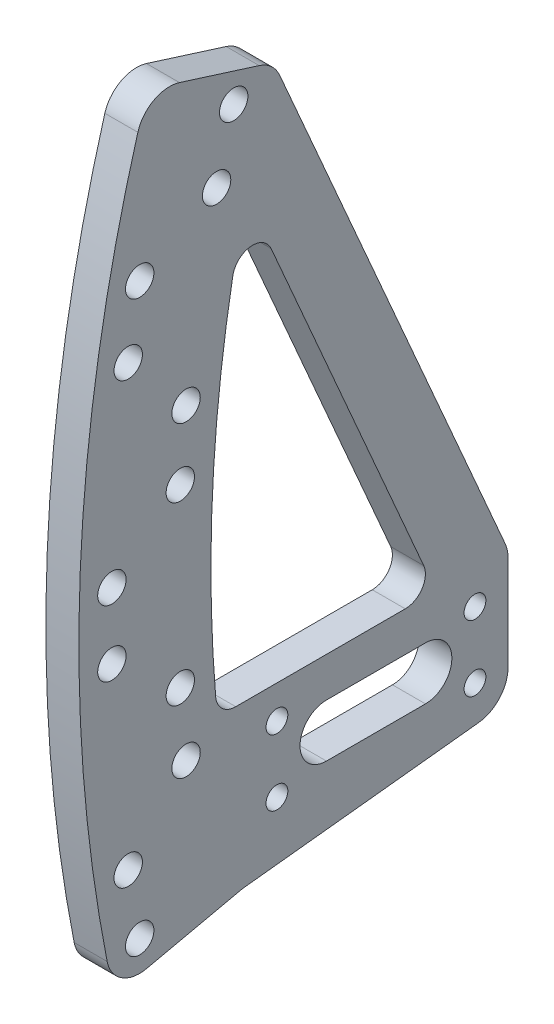
SolidWorks part; units mm, degrees
material "5052-H34"
ref_plane "正面" through (0, 0, 0) normal (0, 0, 1) x (1, 0, 0)
ref_plane "平面" through (0, 0, 0) normal (0, 1, 0) x (1, 0, 0)
ref_plane "右側面" through (0, 0, 0) normal (1, 0, 0) x (0, 0, -1)
sketch "ｽｹｯﾁ1" plane through (0, 0, 0) normal (1, 0, 0) x (0, 0, -1)
  line L0 (0, 0) -> (-220, 0) construction
  line L1 (-220, 0) -> (-220, 5) construction
  line L2 (0, 0) -> (-220, -5) construction
  line L3 (-200, -20) -> (-170.905, -20) construction
  line L4 (-200, -20) -> (-200, -40) construction
  line L5 (-200, -40) -> (-160, -40) construction
  line L6 (0, -20) -> (0, -40) construction
  line L7 (0, 0) -> (-217.5259, 33.2786) construction
  line L8 (0, 0) -> (-209.2009, 18.3027) construction
  line L9 (-209.2009, 18.3027) -> (-208.7651, 23.2837) construction
  line L10 (0, 0) -> (-208.7651, 23.2837) construction
  line L11 (0, 0) -> (-201.5503, 59.1816) construction
  line L12 (-219.6666, 48.6989) -> (-200.1407, 44.3701) construction
  line L13 (-200.1407, 44.3701) -> (0, 0) construction
  line L14 (-219.6666, -48.6989) -> (-200.1407, -44.3701)
  line L15 (-204.0221, -20) -> (-170.905, -20)
  line L16 (-160, -20) -> (-160, -40)
  line L18 (-195, -30) -> (-180, -30) construction
  line L19 (-165, -25) -> (-195, -25) construction
  line L20 (-165, -25) -> (-165, -35) construction
  line L21 (-165, -35) -> (-195, -35) construction
  line L22 (-195, -25) -> (-195, -35) construction
  line L23 (-165, -25) -> (-195, -35) construction
  line L24 (-165, -35) -> (-195, -25) construction
  line L25 (-180, -30) -> (-180, -25) construction
  line L27 (-200.1407, -44.3701) -> (-160, -40)
  line L29 (-187.5, -30) -> (-172.5, -30) construction
  line L30 (-169.1701, -23.9886) -> (-199.7168, 46.2406)
  line L32 (-169.1701, -23.9886) -> (-204.6821, 57.6561) construction
  line L33 (0, 0) -> (-214.5863, 67.6588)
  line L34 (-160, -40) -> (0, -40) construction
  line L35 (-160, -20) -> (0, -20) construction
  line L36 (-160, -20) -> (-195.512, 61.6447)
  line L37 (-187.5, -26) -> (-172.5, -26)
  line L38 (-187.5, -34) -> (-172.5, -34)
  circle A0 centre (-220, 5) radius 2.15
  circle A1 centre (-220, -5) radius 2.15
  circle A2 centre (-217.5259, 33.2786) radius 2.15
  circle A3 centre (-215.7895, 43.1266) radius 2.15
  circle A8 centre (-215.7895, -43.1266) radius 2.15
  circle A9 centre (-217.5259, -33.2786) radius 2.15
  circle A10 centre (-220, -5) radius 2.15
  circle A11 centre (-220, 5) radius 2.15
  circle A12 centre (-208.7651, 23.2837) radius 2.15
  circle A13 centre (-209.6367, 13.3217) radius 2.15
  circle A18 centre (-208.7651, -23.2837) radius 2.15
  circle A19 centre (-209.6367, -13.3217) radius 2.15
  arc A20 (-199.7168, 46.2406) -> (-204.0221, -20) centre (0, 0) ccw
  arc A21 (-219.6666, 48.6989) -> (-219.6666, -48.6989) centre (0, 0) ccw
  circle A22 centre (-165, -25) radius 1.65
  circle A23 centre (-165, -35) radius 1.65
  circle A24 centre (-195, -25) radius 1.65
  circle A25 centre (-195, -35) radius 1.65
  arc A26 (-199.7168, 46.2406) -> (-204.0221, -20) centre (0, 0) ccw
  arc A27 (-187.5, -26) -> (-187.5, -34) centre (-187.5, -30) ccw
  arc A28 (-172.5, -34) -> (-172.5, -26) centre (-172.5, -30) ccw
  arc A29 (-195.512, 61.6447) -> (-196.6958, 57.7562) centre (0, 0) ccw
  circle A30 centre (-204.1385, 49.5224) radius 2.15
  circle A31 centre (-201.5503, 59.1816) radius 2.15
  arc A32 (-214.5863, 67.6588) -> (-219.6666, -48.6989) centre (0, 0) ccw
  arc A33 (-196.6958, 57.7562) -> (-200.1407, 44.3701) centre (0, 0) ccw construction
  point P41 (-200.1407, 47.215)
  point P42 (-170.905, -20)
  point P60 (-180, -30)
  point P82 (-180, -30)
  dimension "D2" = 4.3
  dimension "D14" = 410
  dimension "D15" = 450
  dimension "D22" = 3.3
  dimension "D1" = 220
  dimension "D3" = 10
  dimension "D4" = 20
  dimension "D5" = 20
  dimension "D7" = 10
  dimension "D8" = 200
  dimension "D9" = 10
  dimension "D10" = 5
  dimension "D11" = 210
  dimension "D13" = 2
  dimension "D16" = 12.5
  dimension "D17" = 10
  dimension "D18" = 10
  dimension "D19" = 30
  dimension "D20" = 5
  dimension "D21" = 5
  dimension "D24" = 8
  dimension "D25" = 15
  dimension "D12" = 5
  dimension "D26" = 17.5
  dimension "D23" = 10
  dimension "D6" = 2
extrude "ﾎﾞｽ - 押し出し1" add sketch "ｽｹｯﾁ1" along normal blind 5 contours L12 A21 L14 L27 L16 L15 A20 A26 A25 A23 A22 A18 A8 A3 A1 A0 A2 A9 region at (0, 0, 223.6672)
fillet "ﾌｨﾚｯﾄ1" radius 5 6 edges at (2.5, -44.3701, 200.1407) (2.5, -48.6989, 219.6666) (2.5, -40, 160) (2.5, 67.6588, 214.5863) (2.5, 61.6447, 195.512) (2.5, -20, 160)
fillet "ﾌｨﾚｯﾄ2" radius 3.05 3 edges at (2.5, -20, 204.0221) (2.5, 46.2406, 199.7168) (2.5, -20, 170.905)
